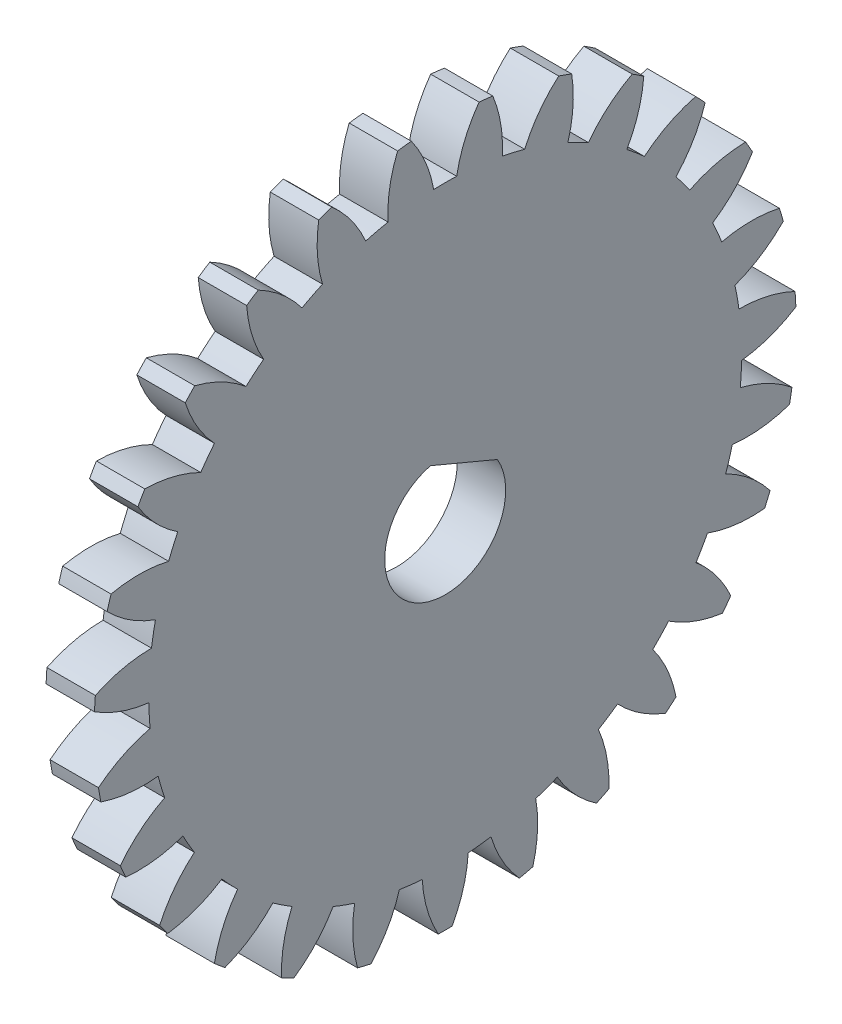
SolidWorks part; units mm, degrees
ref_plane "Plane1" through (0, 0, 0) normal (0, 0, 1) x (1, 0, 0)
ref_plane "Plane2" through (0, 0, 0) normal (0, 1, 0) x (1, 0, 0)
ref_plane "Plane3" through (0, 0, 0) normal (1, 0, 0) x (0, 0, -1)
sketch "HoldingSke" plane through (0, 0, 0) normal (0, 1, 0) x (1, 0, 0)
  line L0 (0, 0) -> (0.891, -0.454)
  line L1 (-15, 0) -> (100, 0) construction
  line L2 (0, 0) -> (-2.1039, 2.3779)
  line L3 (0, 0) -> (-11.863, 4.5341)
  line L4 (0, 0) -> (7.6947, 3.9207)
  line L5 (0, 0) -> (-46.8476, -17.4728)
  line L6 (0, 0) -> (-1.6579, -1.1186)
  line L7 (-2.1039, 2.3779) -> (8.6586, 51.2059)
  line L8 (-76.2, 54.61) -> (-76.1, 54.61)
  line L9 (-71.009, 38.7566) -> (-53.1078, 45.2721)
  line L10 (-76.2, 71.12) -> (104.1128, 71.12)
  line L11 (0, 0) -> (-2, 0)
  line L12 (-76.2, 101.6) -> (-76.162, 101.6)
  line L13 (24.9733, 27.94) -> (52.9518, 28.4284)
  line L14 (24.9733, 27.94) -> (24.9743, 27.94)
  line L15 (24.9733, 27.94) -> (100.4006, 29.5858)
  line L16 (-63.627, -1) -> (-12.827, -1)
  circle A0 centre (0, 0) radius 0.5
  circle A1 centre (0, 0) radius 12.249
  circle A2 centre (0, 0) radius 37.5
  circle A3 centre (0, 0) radius 0.5
  dimension "MHD" = 24.498
  dimension "Hub_dia" = 75
  dimension "Bore" = 1
  dimension "MBD" = 1
  dimension "Num_teeth" = 27
  dimension "Pitch" = 1
  dimension "Overall_len" = 50
  dimension "Show_teeth" = 27
  dimension "Thickness" = 2
  dimension "OAL" = 50.0001
  dimension "T_dim" = 0.1
  dimension "Ap" = 20
  dimension "H" = 19.05
  dimension "Pitch_radius" = 180.3128
  dimension "Width" = 2
  dimension "Backlash" = 0.038
  dimension "Addendum_fac" = 1
  dimension "Dedendum_fac" = 1.25
  dimension "Clearance_fac" = 0.25
  dimension "Dedendum_add" = 0.001
  dimension "Module" = 1
sketch "BasProSke" plane through (0, 0, 0) normal (0, 1, 0) x (1, 0, 0)
  line L0 (-10, 0) -> (60, 0) construction
  line L1 (0, 0) -> (0, 14.5)
  line L2 (0, 0) -> (2, 0)
  line L3 (2, 0) -> (2, 14.5)
  line L4 (2, 14.5) -> (0, 14.5)
  dimension "Thickness" = 2
  dimension "Diameter" = 29
revolve "Base-Revolve" add sketch "BasProSke" angle 360 about L0
sketch "TooCutSke" plane through (0, 0, 0) normal (1, 0, 0) x (0, 0, -1)
  line L1 (0, 0) -> (0, 107) construction
  line L2 (0, 0) -> (-0.8514, 13.4731) construction
  line L3 (0, 0) -> (-3.1301, 26.7794) construction
  line L4 (-0.8514, 13.4731) -> (-1.565, 13.3897) construction
  arc A0 (0.4741, 12.2398) -> (-0.4741, 12.2398) centre (0, 0) ccw
  arc A1 (1.4167, 14.4561) -> (-1.4167, 14.4561) centre (0, 0) ccw
  circle A2 centre (0, 0) radius 13.5 construction
  circle A3 centre (0, 0) radius 12.6859 construction
  arc A4 (-0.4741, 12.2398) -> (-1.4167, 14.4561) centre (-5.7895, 11.2877) ccw
  arc A5 (1.4167, 14.4561) -> (0.4741, 12.2398) centre (5.7895, 11.2877) ccw
  dimension "Root_dia" = 24.498
  dimension "Overcut_dia" = 29.0508
  dimension "Pitch_dia" = 27
  dimension "Base_dia" = 25.3717
  dimension "Flank_rad" = 5.4
  dimension "Half_ang" = 6.667
  dimension "Half_CT" = 0.7185
extrude "ToothCut" cut sketch "TooCutSke" along normal through all
fillet "Breaks" [suppressed] radius 0.02 tangent propagation no
fillet "RootFillets" [suppressed] radius 0.251
pattern_circular "TeethCuts" count 27 every 13.333 about axis through (-10, 0, 0) along (1, 0, 0) of "ToothCut", "RootFillets", "Breaks"
sketch "HubNeaOneSke" plane through (0, 0, 0) normal (-1, 0, 0) x (0, 0, 1)
  circle A0 centre (0, 0) radius 12.249
  dimension "Diameter" = 24.498
extrude "HubNearOne" [suppressed] add sketch "HubNeaOneSke" along normal blind 48.0001
sketch "HubNeaBotSke" plane through (0, 0, 0) normal (-1, 0, 0) x (0, 0, 1)
  circle A0 centre (0, 0) radius 12.249
  dimension "Diameter" = 24.498
extrude "HubNearBoth" [suppressed] add sketch "HubNeaBotSke" along normal blind 24
ref_plane "FarPln" through (2, 0, 0) normal (1, 0, 0) x (0, 0, -1)
sketch "HubFarSke" plane through (2, 0, 0) normal (1, 0, 0) x (0, 0, -1)
  circle A0 centre (0, 0) radius 12.249
  dimension "Diameter" = 24.498
extrude "HubFar" [suppressed] add sketch "HubFarSke" along normal blind 24
sketch "BorSke" plane through (0, 0, 0) normal (1, 0, 0) x (0, 0, -1)
  line L0 (2.1562, 1.2652) -> (-0.6108, 2.4242)
  arc A0 (-0.6108, 2.4242) -> (2.1562, 1.2652) centre (0, 0) ccw
  dimension "D1" = 2.5
  dimension "D2" = 3
extrude "Bore" cut sketch "BorSke" along normal mid plane 100.0001
sketch "KeySke" plane through (0, 0, 0) normal (1, 0, 0) x (0, 0, -1)
  line L0 (-0.05, 0) -> (-0.05, 0.6)
  line L1 (-0.05, 0.6) -> (0.05, 0.6)
  line L2 (0.05, 0.6) -> (0.05, 0)
  line L3 (0, 0) -> (0, 34) construction
  line L4 (-0.05, 0) -> (0.05, 0)
  dimension "Offset" = 0.6
extrude "Keyway" [suppressed] cut sketch "KeySke" along normal mid plane 100.0001
pattern_circular "Keyway2" [suppressed] count 2 every 90 about axis through (-10, 0, 0) along (1, 0, 0) reverse direction yes
equation "' \"Module@HoldingSke\" = 6.35"
equation "' \"Num_teeth@HoldingSke\" = 12"
equation "' \"Ap@HoldingSke\" =  20"
equation "' \"Ap@HoldingSke\" = 20"
equation "' \"Width@HoldingSke\" = 0.5 * 25.4"
equation "' \"Hub_dia@HoldingSke\"= 1 * 25.4"
equation "' \"Hub_dia@HoldingSke\" = 1 * 25.4"
equation "' \"Overall_len@HoldingSke\" = 1.0 * 25.4"
equation "' \"Bore@HoldingSke\" = 0.75 * 25.4"
equation "' \"T_dim@HoldingSke\" = 0.1 * 25.4"
equation "' \"Width@KeySke\" = 0.25 * 25.4"
equation "' \"Show_teeth@HoldingSke\" = 13"
equation "' \"Backlash@HoldingSke\" = 0.009 * 25.4"
equation "' \"Addendum_fac@HoldingSke\" = 1.0"
equation "' \"Dedendum_fac@HoldingSke\" = 1.25"
equation "' \"Dedendum_add@HoldingSke\" = 0.00005 * 25.4"
equation "' \"Clearance_fac@HoldingSke\" = 0.25"
equation "\"Pitch@HoldingSke\" = 1 / \"Module@HoldingSke\""
equation "\"Overcut_dia@TooCutSke\" = (\"Num_teeth@HoldingSke\" + 2 * \"Addendum_fac@HoldingSke\") / \"Pitch@HoldingSke\" + 0.002 * 25.4"
equation "\"Pitch_dia@TooCutSke\" = \"Num_teeth@HoldingSke\" / \"Pitch@HoldingSke\""
equation "\"Base_dia@TooCutSke\" = \"Num_teeth@HoldingSke\" / \"Pitch@HoldingSke\" * cos((\"Ap@HoldingSke\"  * 3.14159265 / 180))"
equation "\"Root_dia@TooCutSke\" = (\"Num_teeth@HoldingSke\" + 2) / \"Pitch@HoldingSke\" - 2 * (\"Addendum_fac@HoldingSke\" + \"Dedendum_fac@HoldingSke\") / \"Pitch@HoldingSke\" - \"Dedendum_add@HoldingSke\" * 2"
equation "\"Half_ang@TooCutSke\" = 180 / \"Num_teeth@HoldingSke\""
equation "\"Half_CT@TooCutSke\" = \"Num_teeth@HoldingSke\" / \"Pitch@HoldingSke\" * sin((3.14159265 / 2 / \"Num_teeth@HoldingSke\")) / 2 - 7 * \"Backlash@HoldingSke\" / 4"
equation "\"Flank_rad@TooCutSke\" = \"Num_teeth@HoldingSke\" / \"Pitch@HoldingSke\" / 5"
equation "\"Radius@RootFillets\" = \"Clearance_fac@HoldingSke\" / \"Pitch@HoldingSke\" + \"Dedendum_add@HoldingSke\""
equation "\"Break_rad@Breaks\" = 0.02 / \"Pitch@HoldingSke\""
equation "\"Thickness@HoldingSke\" = \"Width@HoldingSke\""
equation "\"OAL@HoldingSke\" = \"Thickness@HoldingSke\""
equation "\"MHD@HoldingSke\" = (\"Num_teeth@HoldingSke\" + 2) / \"Pitch@HoldingSke\" - 2 * (\"Addendum_fac@HoldingSke\" + \"Dedendum_fac@HoldingSke\")  / \"Pitch@HoldingSke\" - \"Dedendum_add@HoldingSke\" * 2"
equation "\"MBD@HoldingSke\" = (\"Num_teeth@HoldingSke\" + 2) / \"Pitch@HoldingSke\" - 2 * (\"Addendum_fac@HoldingSke\" + \"Dedendum_fac@HoldingSke\")  / \"Pitch@HoldingSke\" - \"Dedendum_add@HoldingSke\" * 2 - 0.002 * 25.4"
equation "\"MHD@HoldingSke\" = ((sgn( \"MHD@HoldingSke\" - \"Hub_dia@HoldingSke\" )-1)*( \"MHD@HoldingSke\" - \"Hub_dia@HoldingSke\" ))/-2+ \"Hub_dia@HoldingSke\""
equation "\"MBD@HoldingSke\" = ((sgn( \"MBD@HoldingSke\" - \"Bore@HoldingSke\" )-1)*( \"MBD@HoldingSke\" - \"Bore@HoldingSke\" ))/-2+ \"Bore@HoldingSke\""
equation "\"OAL@HoldingSke\" = ((sgn( \"OAL@HoldingSke\" - \"Overall_len@HoldingSke\" )+1)*( \"OAL@HoldingSke\" - \"Overall_len@HoldingSke\" ))/2 + \"Overall_len@HoldingSke\" + 0.000002 * 25.4"
equation "\"Num_teeth@TeethCuts\" = int( \"Show_teeth@HoldingSke\" ) + 1"
equation "\"Num_teeth@TeethCuts\" = ((sgn( \"Num_teeth@TeethCuts\" - \"Num_teeth@HoldingSke\" )-1)*( \"Num_teeth@TeethCuts\" - \"Num_teeth@HoldingSke\" ))/-2+ \"Num_teeth@HoldingSke\""
equation "\"Num_teeth@TeethCuts\" = ((sgn( \"Num_teeth@TeethCuts\" - 2.0)+1)*( \"Num_teeth@TeethCuts\" - 2.0))/2 +2.0"
equation "\"Angle@TeethCuts\" = 360.0 / \"Num_teeth@HoldingSke\""
equation "\"Diameter@BasProSke\" = (\"Num_teeth@HoldingSke\" + 2 * \"Addendum_fac@HoldingSke\") / \"Pitch@HoldingSke\""
equation "\"Thickness@BasProSke\"  = \"Thickness@HoldingSke\""
equation "' \"Fillet_rad@BasProSke\" =  \"Thickness@HoldingSke\" * 0.05"
equation "' \"Fillet_rad@BasProSke\" = \"Thickness@HoldingSke\" * 0.05"
equation "\"MHD@HoldingSke\" = ((sgn( \"MHD@HoldingSke\" - \"Root_dia@TooCutSke\" )-1)*( \"MHD@HoldingSke\" - \"Root_dia@TooCutSke\" ))/-2+ \"Root_dia@TooCutSke\""
equation "\"Diameter@HubNeaOneSke\" = \"MHD@HoldingSke\""
equation "\"Length@HubNearOne\" = \"OAL@HoldingSke\" - \"Thickness@BasProSke\""
equation "\"Diameter@HubNeaBotSke\" = \"MHD@HoldingSke\""
equation "\"Length@HubNearBoth\" = ( \"OAL@HoldingSke\" - \"Thickness@BasProSke\" ) / 2.0"
equation "\"Thickness@FarPln\" = \"Thickness@BasProSke\""
equation "\"Diameter@HubFarSke\" = \"MHD@HoldingSke\""
equation "\"Length@HubFar\" = ( \"OAL@HoldingSke\" - \"Thickness@BasProSke\" ) / 2.0"
equation "\"D1@Bore\" = \"OAL@HoldingSke\" * 2.0"
equation "\"D1@Keyway\" = \"OAL@HoldingSke\" * 2.0"
equation "\"Offset@KeySke\" = \"T_dim@HoldingSke\" + \"MBD@HoldingSke\" / 2.0"
